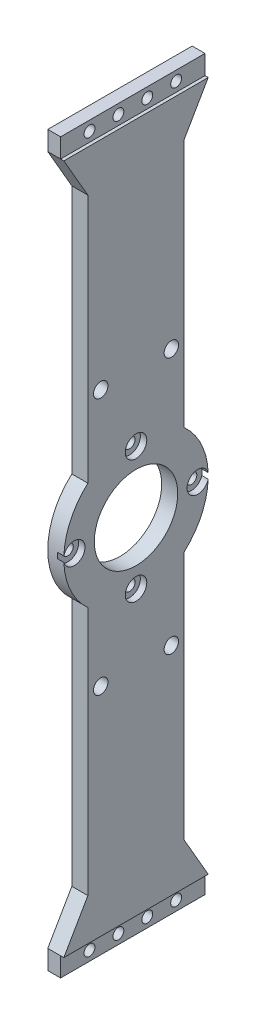
SolidWorks part; units mm, degrees
material "Сплав 2024"
ref_plane "Спереди" through (0, 0, 0) normal (0, 0, 1) x (1, 0, 0)
ref_plane "Сверху" through (0, 0, 0) normal (0, 1, 0) x (1, 0, 0)
ref_plane "Справа" through (0, 0, 0) normal (1, 0, 0) x (0, 0, -1)
sketch "Эскиз1" plane through (0, 0, 0) normal (0, 1, 0) x (1, 0, 0)
  line L1 (0, 0) -> (5, 0)
  line L2 (0, 0) -> (0, -30)
  line L3 (0, -30) -> (5, -30)
  line L4 (5, 0) -> (5, -30)
  dimension "D1" = 5
  dimension "D2" = 30
extrude "Бобышка-Вытянуть1" add sketch "Эскиз1" along normal blind 227
sketch "Эскиз2" plane through (0, 0, 0) normal (-1, 0, 0) x (0, 0, 1)
  line L0 (30, 113.5) -> (0, 113.5) construction
  line L1 (30, 227) -> (30, 0) construction
  line L2 (0, 227) -> (0, 0) construction
  line L3 (15, 227) -> (15, 0) construction
  line L4 (0, 227) -> (30, 227) construction
  line L5 (0, 0) -> (30, 0) construction
  circle A0 centre (15, 113.5) radius 22.5
  dimension "D1" = 45
extrude "Бобышка-Вытянуть2" add sketch "Эскиз2" against normal up to surface (5 mm away) up to face at (5, 113.5, 15)
sketch "Эскиз3" plane through (0, 0, 0) normal (-1, 0, 0) x (0, 0, 1)
  circle A0 centre (15, 113.5) radius 13
  dimension "D1" = 26
extrude "Вырез-Вытянуть1" cut sketch "Эскиз3" against normal through all
sketch "Эскиз4" plane through (5, 0, 0) normal (-1, 0, 0) x (0, 0, 1)
  line L0 (15, 136) -> (15, 91) construction
  line L1 (15, 227) -> (15, 0) construction
  line L2 (37.5, 113.5) -> (-7.5, 113.5) construction
  circle A0 centre (15, 113.5) radius 19.25 construction
  circle A1 centre (15, 113.5) radius 22.5 construction
  dimension "D1" = 38.5
hole_wizard "Цековка для  винта с полукруглой головкой M31" positions "Эскиз6" profile "Эскиз5" counterbore size "M3" standard "Ansi Metric" end condition through all
sketch "Эскиз6" plane through (5, -25.0247, 7.2629) normal (-1, 0, 0) x (0, 0, 1)
  line L0 (7.7371, 161.0247) -> (7.7371, 116.0247) construction
  line L1 (30.2371, 138.5247) -> (-14.7629, 138.5247) construction
  circle A0 centre (7.7371, 138.5247) radius 19.25 construction
  point P0 (7.7371, 157.7747)
  point P6 (-11.5129, 138.5247)
  point P10 (7.7371, 119.2747)
  point P12 (26.9871, 138.5247)
sketch "Эскиз5" plane through (5, 132.75, 15) normal (0, 1, 0) x (0, 0, -1)
  line L0 (0, 0) -> (0, 5)
  line L1 (0, 5) -> (1.7, 5)
  line L3 (1.7, 5) -> (1.7, 2)
  line L4 (1.7, 2) -> (3.35, 2)
  line L5 (3.35, 2) -> (3.35, 0)
  line L7 (3.35, 0) -> (0, 0)
  line L11 (0, -6.35) -> (0, 107.95) construction
  dimension "Диаметр сквозного отверстия" = 3.4
  dimension "Глубина сквозного отверстия" = 5
  dimension "Диаметр цековки" = 6.7
  dimension "Глубина цековки" = 2
sketch "Эскиз8" plane through (5, 0, 0) normal (1, 0, 0) x (0, 0, -1)
  line L0 (-15, 227) -> (-15, 0) construction
  line L1 (-30, 227) -> (0, 227) construction
  line L2 (-30, 0) -> (0, 0) construction
  line L3 (19.447, 113.5) -> (-49.447, 113.5) construction
  line L4 (0, 227) -> (0, 130.2705) construction
  line L5 (-26, 153.5) -> (-4, 153.5) construction
  line L6 (-26, 153.5) -> (-26, 73.5) construction
  line L7 (-26, 73.5) -> (-4, 73.5) construction
  line L8 (-4, 153.5) -> (-4, 73.5) construction
  line L9 (-26, 153.5) -> (-4, 73.5) construction
  line L10 (-26, 73.5) -> (-4, 153.5) construction
  point P8 (-15, 113.5)
  point P9 (-15, 113.5)
  dimension "D1" = 4
  dimension "D2" = 80
hole_wizard "Отверстие с зазором M41" positions "Эскиз10" profile "Эскиз9" hole size "M4" standard "Ansi Metric" end condition through all
sketch "Эскиз10" plane through (5, 0, 0) normal (1, 0, 0) x (0, 0, -1)
  point P0 (-26, 153.5)
  point P3 (-4, 153.5)
  point P6 (-4, 73.5)
  point P9 (-26, 73.5)
sketch "Эскиз9" plane through (5, 153.5, 26) normal (0, 1, 0) x (0, 0, -1)
  line L0 (0, 0) -> (0, 5)
  line L1 (0, 5) -> (2.25, 5)
  line L2 (2.25, 5) -> (2.25, 0)
  line L5 (2.25, 0) -> (0, 0)
  line L11 (0, -6.35) -> (0, 107.95) construction
  dimension "Диаметр сквозного отверстия" = 4.5
  dimension "Глубина сквозного отверстия" = 5
sketch "Эскиз11" plane through (5, 0, 0) normal (1, 0, 0) x (0, 0, -1)
  line L0 (-15, 227) -> (-15, 0) construction
  line L1 (-30, 227) -> (0, 227) construction
  line L2 (-30, 0) -> (0, 0) construction
  line L3 (-37.5, 221) -> (-30, 208.0096)
  line L4 (-37.5, 221) -> (7.5, 221) construction
  line L5 (-37.5, 221) -> (-37.5, 227)
  line L6 (-37.5, 227) -> (7.5, 227)
  line L7 (7.5, 221) -> (7.5, 227)
  line L8 (-37.5, 221) -> (7.5, 227) construction
  line L9 (-37.5, 227) -> (7.5, 221) construction
  line L10 (-30, 227) -> (-30, 130.2705) construction
  line L11 (-30, 208.0096) -> (0, 208.0096)
  line L12 (0, 227) -> (0, 130.2705) construction
  line L13 (0, 208.0096) -> (7.5, 221)
  line L14 (-37.5, 224) -> (7.5, 224) construction
  line L15 (-28.5, 227) -> (-28.5, 221) construction
  line L16 (-19.5, 227) -> (-19.5, 221) construction
  line L17 (-10.5, 227) -> (-10.5, 221) construction
  line L18 (-1.5, 227) -> (-1.5, 221) construction
  line L19 (-15, 113.5) -> (-5.455, 113.5) construction
  line L20 (-1.5, 0) -> (-1.5, 6) construction
  line L21 (-10.5, 0) -> (-10.5, 6) construction
  line L22 (-19.5, 0) -> (-19.5, 6) construction
  line L23 (-28.5, 0) -> (-28.5, 6) construction
  line L24 (-37.5, 3) -> (7.5, 3) construction
  line L25 (-37.5, 0) -> (7.5, 6) construction
  line L26 (-37.5, 6) -> (7.5, 0) construction
  line L27 (-37.5, 6) -> (7.5, 6) construction
  line L28 (0, 18.9904) -> (7.5, 6)
  line L29 (-30, 18.9904) -> (0, 18.9904)
  line L30 (7.5, 6) -> (7.5, 0)
  line L31 (-37.5, 0) -> (7.5, 0)
  line L32 (-37.5, 6) -> (-37.5, 0)
  line L33 (-37.5, 6) -> (-30, 18.9904)
  point P6 (-15, 224)
  point P45 (-15, 3)
  dimension "D1" = 6
  dimension "D2" = 45
  dimension "D3" = 120
  dimension "D4" = 9
  dimension "D5" = 9
  dimension "D6" = 9
  dimension "D7" = 9
extrude "Бобышка-Вытянуть3" add sketch "Эскиз11" against normal up to surface (5 mm away) up to face at (0, 153.5, 23.75)
hole_wizard "Отверстие с зазором M31" positions "Эскиз13" profile "Эскиз12" hole size "M3" standard "Ansi Metric" end condition through all
sketch "Эскиз13" plane through (5, 0, 0) normal (1, 0, 0) x (0, 0, -1)
  line L0 (-28.5, 227) -> (-28.5, 221) construction
  line L1 (-19.5, 227) -> (-19.5, 221) construction
  line L2 (-10.5, 227) -> (-10.5, 221) construction
  line L3 (-1.5, 227) -> (-1.5, 221) construction
  line L4 (-28.5, 0) -> (-28.5, 6) construction
  line L5 (-19.5, 0) -> (-19.5, 6) construction
  line L6 (-10.5, 0) -> (-10.5, 6) construction
  line L7 (-1.5, 0) -> (-1.5, 6) construction
  point P0 (-28.5, 224)
  point P4 (-19.5, 224)
  point P8 (-10.5, 224)
  point P12 (-1.5, 224)
  point P16 (-28.5, 3)
  point P20 (-19.5, 3)
  point P24 (-10.5, 3)
  point P28 (-1.5, 3)
sketch "Эскиз12" plane through (5, 224, 28.5) normal (0, 1, 0) x (0, 0, -1)
  line L0 (0, 0) -> (0, 5)
  line L1 (0, 5) -> (1.7, 5)
  line L2 (1.7, 5) -> (1.7, 0)
  line L5 (1.7, 0) -> (0, 0)
  line L11 (0, -6.35) -> (0, 107.95) construction
  dimension "Диаметр сквозного отверстия" = 3.4
  dimension "Глубина сквозного отверстия" = 5
sketch "Эскиз14" plane through (5, 0, 0) normal (1, 0, 0) x (0, 0, -1)
  line L1 (-37.5, 227) -> (7.5, 227)
  line L2 (-37.5, 227) -> (-37.5, 221)
  line L3 (-37.5, 221) -> (7.5, 221)
  line L4 (7.5, 227) -> (7.5, 221)
  line L5 (-37.5, 0) -> (7.5, 0)
  line L6 (-37.5, 0) -> (-37.5, 6)
  line L7 (-37.5, 6) -> (7.5, 6)
  line L8 (7.5, 0) -> (7.5, 6)
extrude "Вырез-Вытянуть2" cut sketch "Эскиз14" against normal blind 1
equation "\"D4@Эскиз11\"=\"D2@Эскиз11\"/5"
equation "\"D5@Эскиз11\"=\"D4@Эскиз11\""
equation "\"D6@Эскиз11\"=\"D4@Эскиз11\""
equation "\"D7@Эскиз11\"=\"D4@Эскиз11\""
